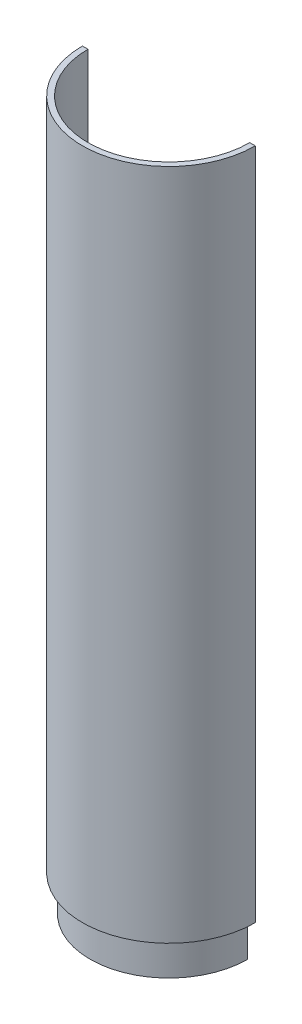
SolidWorks part; units mm, degrees
ref_plane "Front Plane" through (0, 0, 0) normal (0, 0, 1) x (1, 0, 0)
ref_plane "Top Plane" through (0, 0, 0) normal (0, 1, 0) x (1, 0, 0)
ref_plane "Right Plane" through (0, 0, 0) normal (1, 0, 0) x (0, 0, -1)
sketch "Sketch1" plane through (0, 0, 0) normal (0, 1, 0) x (1, 0, 0)
  circle A0 centre (0, 0) radius 49.4538
  dimension "D1" = 98.9076
extrude "Boss-Extrude1" add sketch "Sketch1" along normal blind 3.81 and the other way blind 6.35
sketch "Sketch2" plane through (0, 3.81, 0) normal (0, 1, 0) x (1, 0, 0)
  circle A0 centre (0, 0) radius 49.4538
  dimension "D1" = 98.9076
extrude "Boss-Extrude2" add sketch "Sketch2" along normal blind 381
shell "Shell1" thickness 3.175 removed face at (0, 384.81, 49.4538)
sketch "Sketch4" plane through (0, -6.35, 0) normal (0, -1, 0) x (1, 0, 0)
  line L0 (49.4538, 0) -> (12.7, 0)
  line L1 (-12.7, 0) -> (-49.4538, 0)
  circle A0 centre (0, 0) radius 49.4538 construction
  arc A1 (-12.7, 0) -> (12.7, 0) centre (0, 0) ccw
  arc A2 (-49.4538, 0) -> (49.4538, 0) centre (0, 0) ccw
  dimension "D1" = 25.4
extrude "Cut-Extrude1" cut sketch "Sketch4" against normal through all contours A2 L0 A1 L1
sketch "Sketch5" plane through (0, -3.175, 0) normal (0, 1, 0) x (1, 0, 0)
  line L0 (-46.2788, 0) -> (-12.7, 0)
  line L1 (12.7, 0) -> (46.2788, 0)
  arc A0 (-46.2788, 0) -> (46.2788, 0) centre (0, 0) ccw
  arc A1 (12.7, 0) -> (-12.7, 0) centre (0, 0) ccw
  dimension "D1" = 25.4
extrude "Boss-Extrude3" add sketch "Sketch5" along normal blind 3.81
sketch "Sketch7" plane through (0, -6.35, 0) normal (0, -1, 0) x (1, 0, 0)
  circle A0 centre (0, 0) radius 49.4538
  circle A1 centre (0, 0) radius 45.085
  dimension "D1" = 98.9076
  dimension "D2" = 90.17
extrude "Cut-Extrude2" cut sketch "Sketch7" against normal blind 6.35
sketch "Sketch9" plane through (0, -6.35, 0) normal (0, -1, 0) x (1, 0, 0)
  line L0 (45.085, 0) -> (12.7, 0)
  line L1 (-12.7, 0) -> (-45.085, 0)
  arc A0 (45.085, 0) -> (-45.085, 0) centre (0, 0) ccw
  arc A1 (-12.7, 0) -> (12.7, 0) centre (0, 0) ccw
  dimension "D2" = 25.4
extrude "Boss-Extrude4" add sketch "Sketch9" along normal blind 7.62 contours A0 L1 A1 L0
sketch "Sketch10" plane through (0, 0.635, 0) normal (0, 1, 0) x (1, 0, 0)
  circle A2 centre (0, 0) radius 16.51
  circle A3 centre (0, 0) radius 35.56
  dimension "D1" = 33.02
  dimension "D2" = 71.12
extrude "Cut-Extrude3" cut sketch "Sketch10" against normal blind 6.35 contours A3
sketch "Sketch11" plane through (0, -5.715, 0) normal (0, 1, 0) x (1, 0, 0)
  circle A0 centre (0, 0) radius 8.382
  dimension "D1" = 16.764
extrude "Cut-Extrude4" cut sketch "Sketch11" against normal blind 5.08
sketch "Sketch12" plane through (0, -10.795, 0) normal (0, 1, 0) x (1, 0, 0)
  circle A0 centre (0, 0) radius 6.0325
  dimension "D1" = 12.065
extrude "Cut-Extrude5" cut sketch "Sketch12" against normal through all
sketch "Sketch13" plane through (0, 0.635, 0) normal (0, 1, 0) x (1, 0, 0)
  line L0 (-46.2788, 0) -> (-35.56, 0)
  line L1 (35.56, 0) -> (46.2788, 0)
  arc A0 (-46.2788, 0) -> (46.2788, 0) centre (0, 0) ccw
  arc A1 (-35.56, 0) -> (35.56, 0) centre (0, 0) ccw
extrude "Boss-Extrude5" add sketch "Sketch13" along normal blind 5.08
sketch "Sketch14" plane through (0, -13.97, 0) normal (0, -1, 0) x (1, 0, 0)
  circle A0 centre (0, 15.24) radius 4.191
  dimension "D1" = 8.382
  dimension "D2" = 15.24
extrude "Cut-Extrude6" cut sketch "Sketch14" against normal through all
sketch "Sketch15" plane through (0, -13.97, 0) normal (0, -1, 0) x (1, 0, 0)
  line L2 (12.7, 0) -> (45.085, 0)
  line L3 (-45.085, 0) -> (-12.7, 0)
  line L4 (12.7, 0) -> (45.085, 0)
  line L5 (-45.085, 0) -> (-12.7, 0)
  circle A0 centre (0, 15.24) radius 4.191 construction
  circle A1 centre (0, 0) radius 6.0325 construction
  arc A2 (45.085, 0) -> (-45.085, 0) centre (0, 0) ccw
  arc A3 (-12.7, 0) -> (12.7, 0) centre (0, 0) ccw
  arc A4 (45.085, 0) -> (-45.085, 0) centre (0, 0) ccw
  arc A5 (-12.7, 0) -> (12.7, 0) centre (0, 0) ccw
  circle A6 centre (0, 15.24) radius 4.191
  circle A7 centre (0, 0) radius 6.0325
  dimension "D1" = 0
extrude "Boss-Extrude6" add sketch "Sketch15" along normal blind 6.35
ref_plane "Plane1" through (0, -13.0175, 0) normal (0, -1, 0) x (-1, 0, 0)
mirror "Mirror2" about plane through (0, -13.0175, 0) normal (0, -1, 0) of "Cut-Extrude4"
